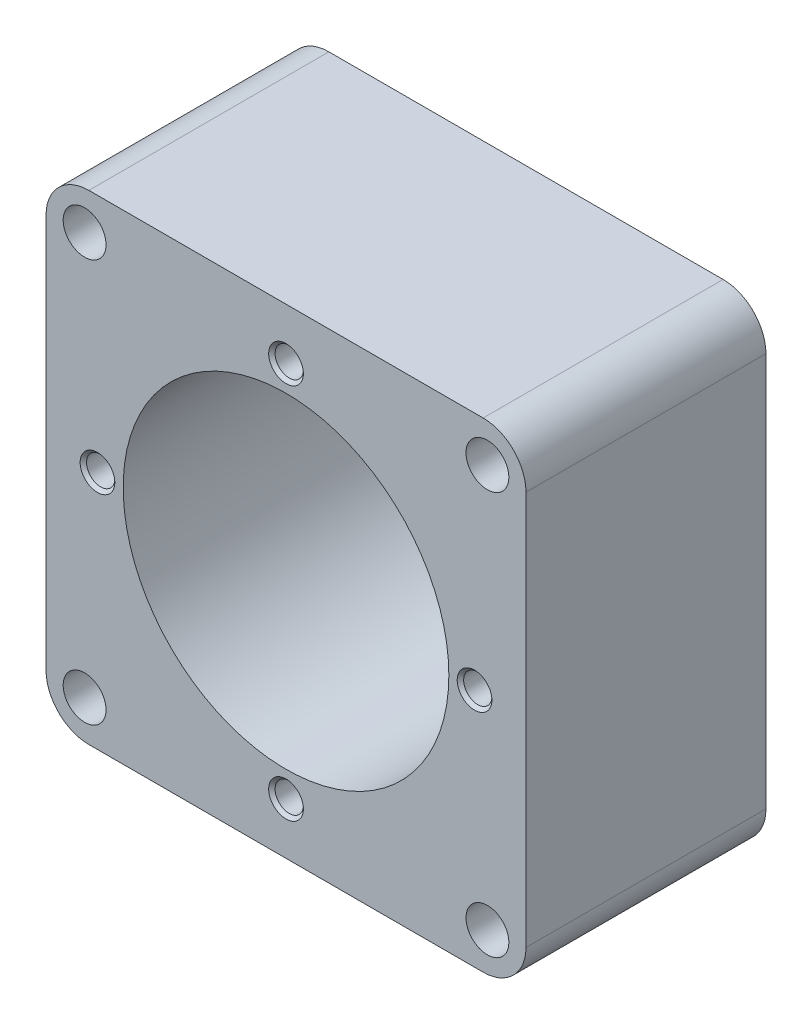
SolidWorks part; units mm, degrees
ref_plane "Front Plane" through (0, 0, 0) normal (0, 0, 1) x (1, 0, 0)
ref_plane "Top Plane" through (0, 0, 0) normal (0, 1, 0) x (1, 0, 0)
ref_plane "Right Plane" through (0, 0, 0) normal (1, 0, 0) x (0, 0, -1)
sketch "Sketch1" plane through (0, 0, 0) normal (0, 0, 1) x (1, 0, 0)
  line L1 (-28, -28) -> (28, -28)
  line L2 (-28, -28) -> (-28, 28)
  line L3 (-28, 28) -> (28, 28)
  line L4 (28, -28) -> (28, 28)
  line L5 (-28, -28) -> (28, 28) construction
  line L6 (-28, 28) -> (28, -28) construction
  point P0 (0, 0)
  dimension "D1" = 56
base flange "Base-Flange1" sketch "Sketch1" thickness 28 reverse thickness direction no parameters "D1"=2
sketch "Sketch6" plane through (0, 0, 0) normal (0, 0, 1) x (1, 0, 0)
  line L0 (0, 0) -> (0, 22) construction
  line L1 (-23.5, -23.5) -> (23.5, -23.5) construction
  line L2 (-23.5, -23.5) -> (-23.5, 23.5) construction
  line L3 (-23.5, 23.5) -> (23.5, 23.5) construction
  line L4 (23.5, -23.5) -> (23.5, 23.5) construction
  line L5 (-23.5, -23.5) -> (23.5, 23.5) construction
  line L6 (-23.5, 23.5) -> (23.5, -23.5) construction
  circle A0 centre (0, 0) radius 19
  circle A1 centre (-23.5, 23.5) radius 2.5
  circle A2 centre (23.5, 23.5) radius 2.5
  circle A3 centre (23.5, -23.5) radius 2.5
  circle A4 centre (-23.5, -23.5) radius 2.5
  circle A5 centre (0, 0) radius 22 construction
  dimension "D1" = 38
  dimension "D3" = 5
  dimension "D4" = 44
  dimension "D2" = 47
extrude "Cut-Extrude1" cut sketch "Sketch6" against normal through all
sketch "Sketch9" plane through (0, 0, 0) normal (0, 0, 1) x (1, 0, 0)
  line L0 (0, 0) -> (0, 22) construction
  circle A0 centre (0, 0) radius 22 construction
  circle A1 centre (0, 22) radius 4.5
  circle A2 centre (22, 0) radius 4.5
  circle A3 centre (0, -22) radius 4.5
  circle A4 centre (-22, 0) radius 4.5
  point P14 (0, 0)
  dimension "D1" = 44
  dimension "D2" = 9
  dimension "D3" = 4
fillet "Fillet1" radius 5 4 edges at (28, -28, -14) (-28, -28, -14) (-28, 28, -14) (28, 28, -14)
hole_wizard "M4x0.7 Tapped Hole1" positions "Sketch10" profile "Sketch11" tap size "M4x0.7" standard "ANSI Metric"
sketch "Sketch10" plane through (0, 0, 0) normal (0, 0, 1) x (1, 0, 0)
  point P0 (0, 22)
  point P3 (-22, 0)
  point P6 (0, -22)
  point P9 (22, 0)
sketch "Sketch11" plane through (0, 22, 0) normal (1, 0, 0) x (0, -1, 0)
  line L0 (0, 0) -> (0, 13.0914)
  line L1 (0, 13.0914) -> (1.65, 12.1)
  line L2 (1.65, 12.1) -> (1.65, 0.375)
  line L3 (1.65, 0.375) -> (2.025, 0)
  line L5 (2.025, 0) -> (0, 0)
  line L6 (-1.65, 0.375) -> (-2.025, 0) construction
  line L10 (0, 13.0914) -> (-1.65, 12.1) construction
  line L11 (0, -6.35) -> (0, 107.95) construction
  dimension "Tap Drill Dia." = 3.3
  dimension "Tap Drill Depth" = 12.1
  dimension "Near C'Sink Dia." = 4.05
  dimension "Near C'Sink Angle" = 90
  dimension "Drill Angle" = 118
sketch "Bend-Lines1" [suppressed] plane through (0, 0, 0) normal (0, 1, 0) x (1, 0, 0)
sketch "Bounding-Box1" [suppressed] plane through (0, 0, 0) normal (0, 1, 0) x (1, 0, 0)
sheet metal parameters "Sheet-Metal1" thickness 28 parameters "D1"=2
flat pattern "Flat-Pattern1" [suppressed]
sketch "Bend-Lines2" plane through (0, 0, 0) normal (0, 1, 0) x (1, 0, 0)
sketch3d "Bounding-Box2" [suppressed]
  line L0 (28, -28, 0) -> (-28, -28, 0) construction
  line L1 (28, 28, 0) -> (-28, 28, 0) construction
  line L2 (28, -28, 0) -> (28, 28, 0) construction
  line L3 (-28, -28, 0) -> (-28, 28, 0) construction
sheet metal parameters "Sheet-Metal2" thickness 28 parameters "D1"=2
flat pattern "Flat-Pattern1"
sketch "Bend-Lines2" plane through (0, 0, 0) normal (0, 1, 0) x (1, 0, 0)
sketch3d "Bounding-Box2" [suppressed]
  line L0 (28, -28, 0) -> (28, 28, 0) construction
  line L1 (-28, -28, 0) -> (-28, 28, 0) construction
  line L2 (28, -28, 0) -> (-28, -28, 0) construction
  line L3 (28, 28, 0) -> (-28, 28, 0) construction
sheet metal parameters "Sheet-Metal5" thickness 28 parameters "D1"=2
flat pattern "Flat-Pattern1"
sketch "Bend-Lines2" plane through (0, 0, 0) normal (0, 1, 0) x (1, 0, 0)
sketch3d "Bounding-Box2" [suppressed]
  line L0 (28, -28, 0) -> (28, 28, 0) construction
  line L1 (-28, -28, 0) -> (-28, 28, 0) construction
  line L2 (28, -28, 0) -> (-28, -28, 0) construction
  line L3 (28, 28, 0) -> (-28, 28, 0) construction
